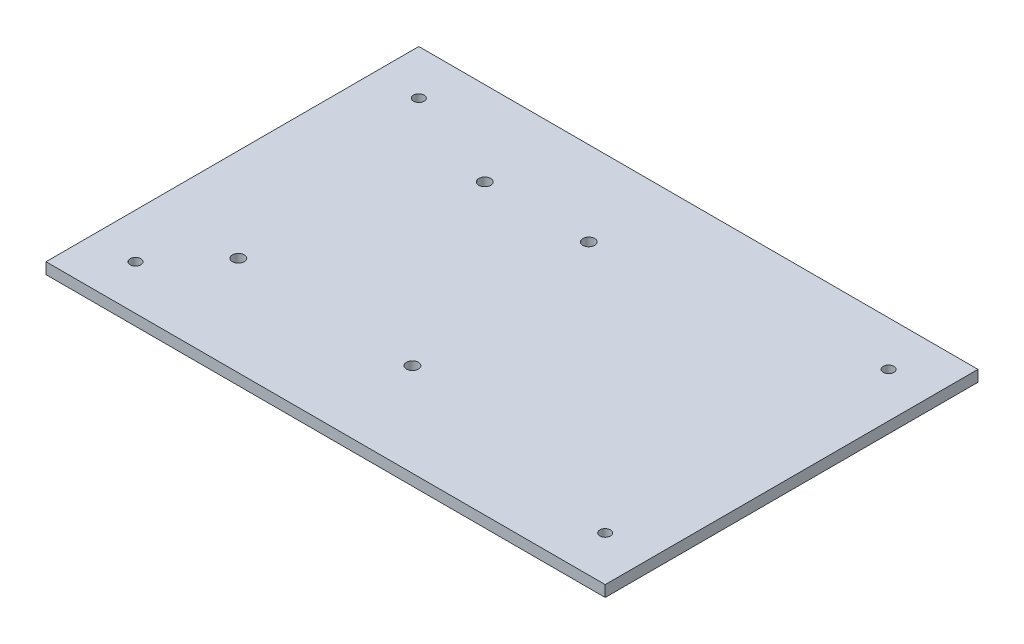
SolidWorks part; units mm, degrees
ref_plane "Front Plane" through (0, 0, 0) normal (0, 0, 1) x (1, 0, 0)
ref_plane "Top Plane" through (0, 0, 0) normal (0, 1, 0) x (1, 0, 0)
ref_plane "Right Plane" through (0, 0, 0) normal (1, 0, 0) x (0, 0, -1)
sketch "Sketch1" plane through (0, 0, 0) normal (0, 1, 0) x (1, 0, 0)
  line L1 (75, -50) -> (-75, -50)
  line L2 (75, -50) -> (75, 50)
  line L3 (75, 50) -> (-75, 50)
  line L4 (-75, -50) -> (-75, 50)
  line L5 (75, -50) -> (-75, 50) construction
  line L6 (75, 50) -> (-75, -50) construction
  point P0 (0, 0)
  dimension "D1" = 150
  dimension "D2" = 100
extrude "Boss-Extrude1" add sketch "Sketch1" along normal blind 3
sketch "Sketch2" plane through (0, 3, 0) normal (0, 1, 0) x (1, 0, 0)
  line L0 (0, 0) -> (-122.3191, 0) construction
  line L1 (-122.3191, 0) -> (115.1579, 0) construction
  line L2 (0, 73.5477) -> (0, -98.9538) construction
  line L3 (75, 50) -> (-75, 50) construction
  line L4 (-75, 50) -> (-75, -50) construction
  circle A0 centre (-63, 38) radius 1.425
  dimension "D1" = 2.85
  dimension "D2" = 12
  dimension "D3" = 12
extrude "Cut-Extrude1" cut sketch "Sketch2" against normal blind 10
pattern_linear "LPattern1" count 1 spacing 126 along (1, 0, 0) count 2 spacing 76 along (0, 0, 1) of "Cut-Extrude1"
sketch "Sketch3" [suppressed] plane through (0, 3, 0) normal (0, 1, 0) x (1, 0, 0)
  line L0 (47, 37) -> (-47, 37) construction
  line L1 (-47, 37) -> (-47, -37) construction
  circle A0 centre (-38, 28) radius 1.425
  dimension "D1" = 2.85
  dimension "D2" = 9
  dimension "D3" = 9
extrude "Cut-Extrude2" [suppressed] cut sketch "Sketch3" against normal blind 10
pattern_linear "LPattern2" [suppressed] count 2 spacing 76 count 2 spacing 56 of bodies 104
sketch "Sketch4" [suppressed] plane through (0, 3, 0) normal (0, 1, 0) x (1, 0, 0)
  line L0 (75, 37) -> (-75, 37) construction
  line L1 (-75, 37) -> (-75, -37) construction
  circle A0 centre (-63, 28) radius 1.425
  dimension "D1" = 2.85
  dimension "D2" = 9
  dimension "D3" = 12
extrude "Cut-Extrude3" [suppressed] cut sketch "Sketch4" against normal blind 10
pattern_linear "LPattern3" [suppressed] count 2 spacing 126 count 2 spacing 56 of bodies 106
sketch "Sketch5" plane through (0, 3, 0) normal (0, 1, 0) x (1, 0, 0)
  line L0 (-75, 50) -> (-75, -50) construction
  line L1 (-75, -50) -> (75, -50) construction
  line L3 (-1.7, -25) -> (-81.1724, -25) construction
  line L4 (-6.8, 27.4) -> (-34.7, 27.4) construction
  circle A0 centre (-34.7, 27.4) radius 1.6
  circle A1 centre (-6.8, 27.4) radius 1.6
  circle A2 centre (-1.7, -25) radius 1.6
  circle A4 centre (-50, -23.4) radius 1.6
  dimension "D1" = 3.2
  dimension "D2" = 27.9
  dimension "D3" = 5.1
  dimension "D4" = 50.8
  dimension "D5" = 48.3
  dimension "D6" = 25
  dimension "D7" = 25
extrude "Cut-Extrude4" cut sketch "Sketch5" against normal blind 10
sketch "Sketch6" plane through (0, 0, 0) normal (0, -1, 0) x (1, 0, 0)
  line L0 (-63, 38) -> (100.028, 38) construction
  line L1 (75, 50) -> (75, -50) construction
  line L2 (63, 38) -> (63, -100.5192) construction
  line L3 (-63, -38) -> (102.189, -38) construction
  circle A0 centre (63, 38) radius 1.425
  circle A3 centre (63, -38) radius 1.425
  dimension "D2" = 2.85
  dimension "D1" = 12
extrude "Cut-Extrude5" cut sketch "Sketch6" against normal blind 10
sketch "Sketch7" [suppressed] plane through (0, 3, 0) normal (0, 1, 0) x (1, 0, 0)
  line L0 (-47, 37) -> (-47, -37) construction
  line L1 (47, 37) -> (-47, 37)
  line L2 (47, 37) -> (47, 35.24)
  line L3 (47, 35.24) -> (-47, 35.24)
  line L4 (-47, 37) -> (-47, 35.24)
  dimension "D1" = 1.76
extrude "Cut-Extrude6" [suppressed] cut sketch "Sketch7" against normal blind 10
sketch "Sketch8" [suppressed] plane through (-47, 0, 0) normal (-1, 0, 0) x (0, 0, 1)
  line L0 (-35.24, 0) -> (37, 0) construction
  line L1 (-35.24, 3) -> (-20.24, 3)
  line L2 (-35.24, 3) -> (-35.24, 0)
  line L3 (-35.24, 0) -> (-20.24, 0)
  line L4 (-20.24, 3) -> (-20.24, 0)
  dimension "D1" = 15
extrude "Boss-Extrude2" [suppressed] add sketch "Sketch8" along normal blind 3
mirror "Mirror1" [suppressed] about plane through (0, 0, 0) normal (1, 0, 0)
sketch "Sketch9" [suppressed] plane through (0, 3, 0) normal (0, 1, 0) x (1, 0, 0)
  line L0 (-75, -50) -> (75, -50) construction
  line L1 (75, 50) -> (70.31, 50)
  line L2 (75, 50) -> (75, -50)
  line L3 (75, -50) -> (70.31, -50)
  line L4 (70.31, 50) -> (70.31, -50)
  dimension "D1" = 4.69
extrude "Cut-Extrude7" [suppressed] cut sketch "Sketch9" against normal blind 10
